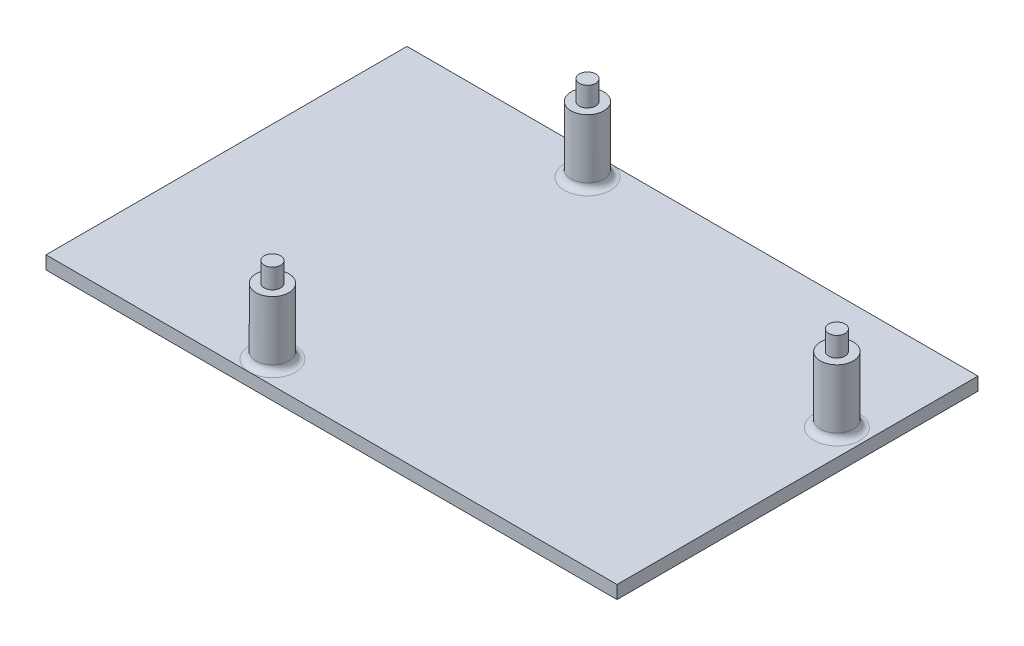
SolidWorks part; units mm, degrees
ref_plane "Front Plane" through (0, 0, 0) normal (0, 0, 1) x (1, 0, 0)
ref_plane "Top Plane" through (0, 0, 0) normal (0, 1, 0) x (1, 0, 0)
ref_plane "Right Plane" through (0, 0, 0) normal (1, 0, 0) x (0, 0, -1)
sketch "Sketch1" plane through (0, 0, 0) normal (0, 1, 0) x (1, 0, 0)
  line L1 (0, 0) -> (87, 0)
  line L2 (0, 0) -> (0, 55)
  line L3 (0, 55) -> (87, 55)
  line L4 (87, 0) -> (87, 55)
  line L13 (0, 62.5) -> (84, 62.5) construction
  line L14 (0, 62.5) -> (0, -7.5) construction
  line L15 (0, -7.5) -> (84, -7.5) construction
  line L16 (84, 62.5) -> (84, -7.5) construction
  dimension "D2" = 55
  dimension "D3" = 3
  dimension "D8" = 84
  dimension "D9" = 70
  dimension "D10" = 7.5
extrude "Boss-Extrude1" add sketch "Sketch1" along normal blind 2
sketch "Sketch2" plane through (0, 2, 0) normal (0, 1, 0) x (1, 0, 0)
  line L0 (84, 62.5) -> (84, -7.5) construction
  line L1 (0, 62.5) -> (84, 62.5) construction
  line L2 (0, -7.5) -> (84, -7.5) construction
  circle A0 centre (31, 51.5) radius 2.5
  circle A1 centre (31, 3.5) radius 2.5
  circle A2 centre (83, 37.5) radius 2.5
  dimension "D1" = 5
  dimension "D2" = 53
  dimension "D3" = 25
  dimension "D4" = 11
  dimension "D5" = 11
  dimension "D6" = 1
extrude "Boss-Extrude2" add sketch "Sketch2" along normal blind 10
sketch "Sketch3" plane through (0, 12, 0) normal (0, 1, 0) x (1, 0, 0)
  circle A0 centre (31, 51.5) radius 1.25
  circle A1 centre (31, 3.5) radius 1.25
  circle A2 centre (83, 37.5) radius 1.25
  dimension "D1" = 2.5
extrude "Boss-Extrude3" add sketch "Sketch3" along normal blind 3
fillet "Fillet2" radius 1 3 edges at (83, 2, -40) (31, 2, -6) (31, 2, -54)
